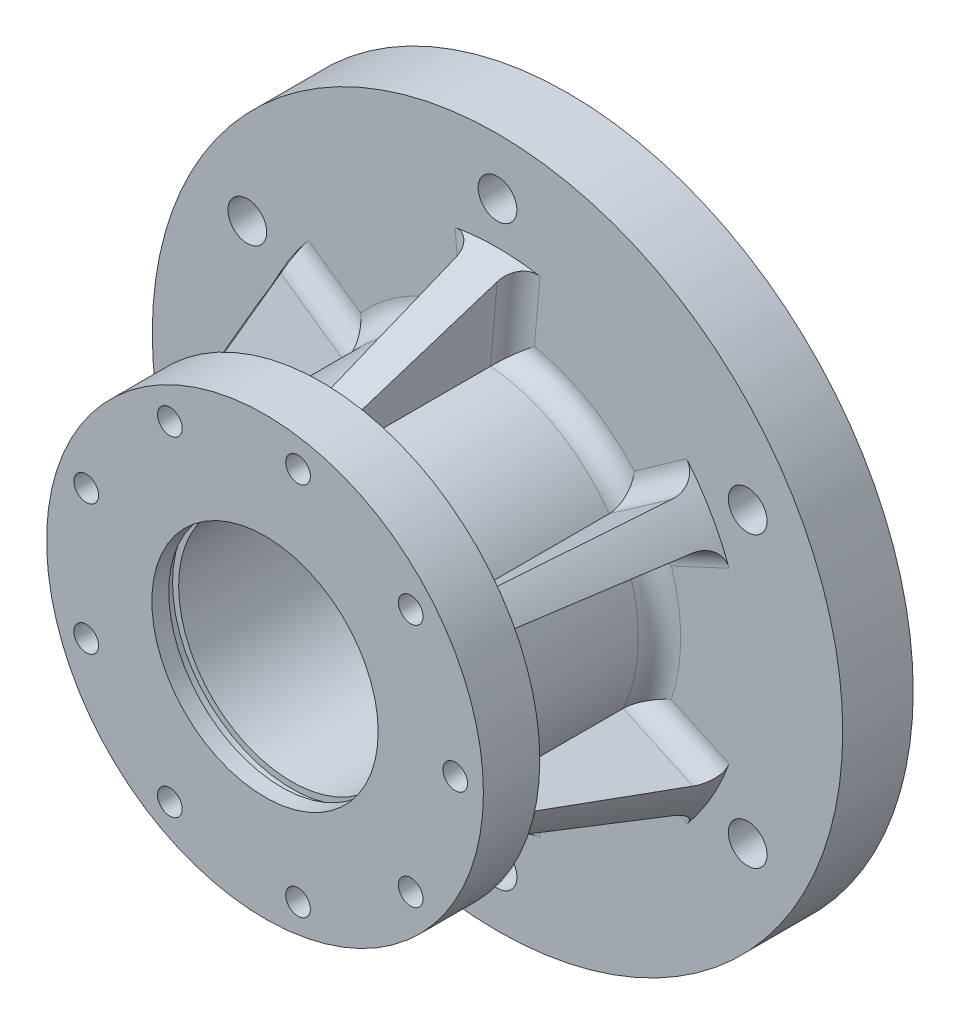
SolidWorks part; units mm, degrees
material "ABS generico"
ref_plane "Piano frontale" through (0, 0, 0) normal (0, 0, 1) x (1, 0, 0)
ref_plane "Piano superiore" through (0, 0, 0) normal (0, 1, 0) x (1, 0, 0)
ref_plane "Piano destro" through (0, 0, 0) normal (1, 0, 0) x (0, 0, -1)
sketch "Schizzo1" plane through (0, 0, 0) normal (0, 0, 1) x (1, 0, 0)
  circle A0 centre (0, 0) radius 49
  circle A1 centre (0, 0) radius 35
  dimension "D1" = 70
  dimension "D2" = 98
extrude "Estrusione-Estrusione1" add sketch "Schizzo1" along normal blind 10
sketch "Schizzo2" plane through (0, 0, 10) normal (0, 0, 1) x (1, 0, 0)
  circle A0 centre (0, 0) radius 41 construction
  circle A1 centre (0, 41) radius 2.75
  dimension "D1" = 82
  dimension "D2" = 5.5
extrude "Taglio-Estrusione1" cut sketch "Schizzo2" against normal through all
pattern_circular "RipetizioneCircolare1" count 6 over 360 about axis through (0, 0, 10) along (0, 0, -1) of "Taglio-Estrusione1" reverse direction yes
sketch "Schizzo4" plane through (0, 0, 10) normal (0, 0, 1) x (1, 0, 0)
  circle A0 centre (0, 0) radius 35
  dimension "D1" = 70
extrude "Estrusione-Estrusione2" add sketch "Schizzo4" against normal blind 4
sketch "Schizzo5" plane through (0, 0, 10) normal (0, 0, 1) x (1, 0, 0)
  circle A0 centre (0, 0) radius 16
  circle A1 centre (0, 0) radius 23
  dimension "D1" = 32
  dimension "D2" = 7
extrude "Estrusione-Estrusione3" add sketch "Schizzo5" along normal blind 33
sketch "Schizzo6" plane through (0, 0, 10) normal (0, 0, 1) x (1, 0, 0)
  circle A0 centre (0, 0) radius 16
  circle A1 centre (0, 0) radius 16 construction
extrude "Taglio-Estrusione2" cut sketch "Schizzo6" against normal through all
sketch "Schizzo8" plane through (0, 0, 6) normal (0, 0, -1) x (-1, 0, 0)
  circle A0 centre (0, 0) radius 16
  circle A1 centre (0, 0) radius 14
  circle A2 centre (0, 0) radius 16 construction
  dimension "D1" = 2
extrude "Estrusione-Estrusione4" add sketch "Schizzo8" against normal blind 2 from offset 3 offset against normal yes
chamfer "Smusso1" distance 4 angle 45 1 edges at (35, 0, 6)
chamfer "Smusso2" distance 2 angle 45 1 edges at (16, 0, 6)
sketch "Schizzo9" plane through (0, 0, 0) normal (0, 0, -1) x (-1, 0, 0)
  circle A0 centre (0, 0) radius 35
  circle A1 centre (0, 0) radius 46.5
  circle A2 centre (0, 0) radius 35 construction
  dimension "D1" = 93
extrude "Taglio-Estrusione4" cut sketch "Schizzo9" against normal blind 1
sketch "Schizzo10" plane through (0, 0, 0) normal (1, 0, 0) x (0, 0, -1)
  line L0 (-43, 23) -> (-10, 35)
  line L1 (-10, 49) -> (-10, -49) construction
  line L2 (-10, 35) -> (-10, 23)
  line L3 (-10, 23) -> (-43, 23)
  dimension "D1" = 12
ref_axis "Assi1" through (0, 0, 43) along (0, 0, -1)
revolve "Rivoluzione1" add sketch "Schizzo10" angle 10 mid plane about axis through (0, 0, 43) along (0, 0, -1)
pattern_circular "RipetizioneCircolare3" count 6 over 360 about axis through (0, 0, 10) along (0, 0, 1) of "Rivoluzione1"
fillet "Raccordo1" radius 3 18 edges at (2.5275, 28.8896, 10) (23.7554, 16.6337, 10) (11.5, 19.9186, 10) (-2.5275, 28.8896, 10) (-23.7554, 16.6337, 10) (-11.5, 19.9186, 10) (-26.2829, -12.2559, 10) (-23, 0, 10) (-26.2829, 12.2559, 10) (-2.5275, -28.8896, 10) (-23.7554, -16.6337, 10) (-11.5, -19.9186, 10) (23.7554, -16.6337, 10) (11.5, -19.9186, 10) (2.5275, -28.8896, 10) (26.2829, 12.2559, 10) (26.2829, -12.2559, 10) (23, 0, 10)
other "Sposta faccia1" flip direction yes face at (-46.5, 0, 1) face at (16, 0, 43) offset 0.06 parameters "D1"=0.06
sketch "Schizzo11" plane through (0, 0, 43) normal (0, 0, 1) x (1, 0, 0)
  circle A0 centre (0, 0) radius 16.925
  dimension "D1" = 33.85
extrude "Taglio-Estrusione5" cut sketch "Schizzo11" against normal blind 1.4 from offset 2.4 offset against normal yes
sketch "Schizzo12" plane through (0, 0, 43) normal (0, 0, 1) x (1, 0, 0)
  circle A0 centre (0, 0) radius 31
  circle A1 centre (0, 0) radius 23
  arc A2 (18.8405, 13.1923) -> (2.0046, 22.9125) centre (0, 0) ccw construction
  dimension "D1" = 8
extrude "Estrusione-Estrusione5" add sketch "Schizzo12" against normal blind 8
sketch "Schizzo13" plane through (0, 0, 43) normal (0, 0, 1) x (1, 0, 0)
  line L0 (0, 0) -> (0, 31) construction
  line L1 (0, 0) -> (-13.5, 23.3827) construction
  circle A0 centre (0, 0) radius 27 construction
  circle A1 centre (0, 0) radius 31 construction
  circle A2 centre (-13.5, 23.3827) radius 1.75
  dimension "D1" = 4
  dimension "D2" = 3.5
  dimension "D3" = 30
extrude "Taglio-Estrusione6" cut sketch "Schizzo13" against normal blind 8
sketch "Schizzo14" plane through (0, 0, 35) normal (0, 0, -1) x (-1, 0, 0)
  line L1 (11.8834, 26.1827) -> (10.2668, 23.3827)
  line L2 (10.2668, 23.3827) -> (11.8834, 20.5827)
  line L3 (11.8834, 20.5827) -> (15.1166, 20.5827)
  line L4 (15.1166, 20.5827) -> (16.7332, 23.3827)
  line L5 (16.7332, 23.3827) -> (15.1166, 26.1827)
  line L6 (15.1166, 26.1827) -> (11.8834, 26.1827)
  circle A0 centre (13.5, 23.3827) radius 2.8 construction
  point P1 (9.9511, 21.4407)
  point P10 (15.8117, 24.1128)
  dimension "D1" = 5.6
extrude "Taglio-Estrusione7" cut sketch "Schizzo14" against normal blind 2.5
pattern_circular "RipetizioneCircolare4" count 9 over 360 about axis through (0, 0, 43) along (0, 0, -1) of "Taglio-Estrusione7", "Taglio-Estrusione6"
fillet "Raccordo2" radius 3 6 edges at (-23, 0, 35) (-11.5, 19.9186, 35) (11.5, 19.9186, 35) (23, 0, 35) (11.5, -19.9186, 35) (-11.5, -19.9186, 35)
